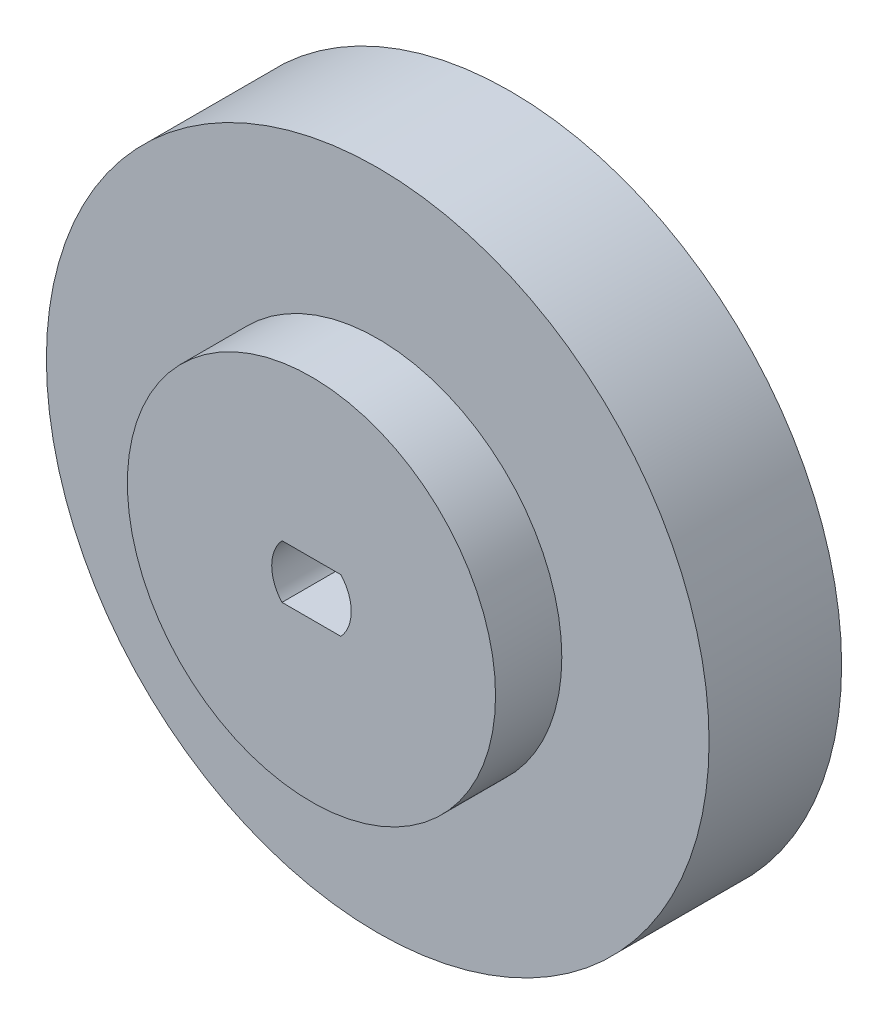
SolidWorks part; units mm, degrees
ref_plane "Front Plane" through (0, 0, 0) normal (0, 0, 1) x (1, 0, 0)
ref_plane "Top Plane" through (0, 0, 0) normal (0, 1, 0) x (1, 0, 0)
ref_plane "Right Plane" through (0, 0, 0) normal (1, 0, 0) x (0, 0, -1)
sketch "Sketch1" plane through (0, 0, 0) normal (0, 0, 1) x (1, 0, 0)
  line L0 (-34.1361, 0) -> (38.3541, 0) construction
  line L1 (0, 21.5067) -> (0, -21.6048) construction
  circle A0 centre (0, -0.049) radius 12.5
  dimension "D1" = 25
extrude "Boss-Extrude1" add sketch "Sketch1" along normal blind 18
sketch "Sketch2" plane through (0, 0, 18) normal (0, 0, 1) x (1, 0, 0)
  circle A0 centre (0, 0) radius 22.5
  dimension "D1" = 45
extrude "Boss-Extrude2" add sketch "Sketch2" against normal blind 9 from offset 4.5 offset against normal yes
sketch "Sketch3" plane through (0, 0, 18) normal (0, 0, 1) x (1, 0, 0)
  line L0 (-9.6925, 0) -> (15.432, 0) construction
  line L1 (-2, 1.8138) -> (2, 1.8138)
  line L2 (-2, -1.8138) -> (2, -1.8138)
  arc A0 (-2, 1.8138) -> (-2, -1.8138) centre (0, 0) ccw
  arc A1 (2, -1.8138) -> (2, 1.8138) centre (0, 0) ccw
  dimension "D1" = 5.4
  dimension "D2" = 4
extrude "Cut-Extrude1" cut sketch "Sketch3" against normal through all
